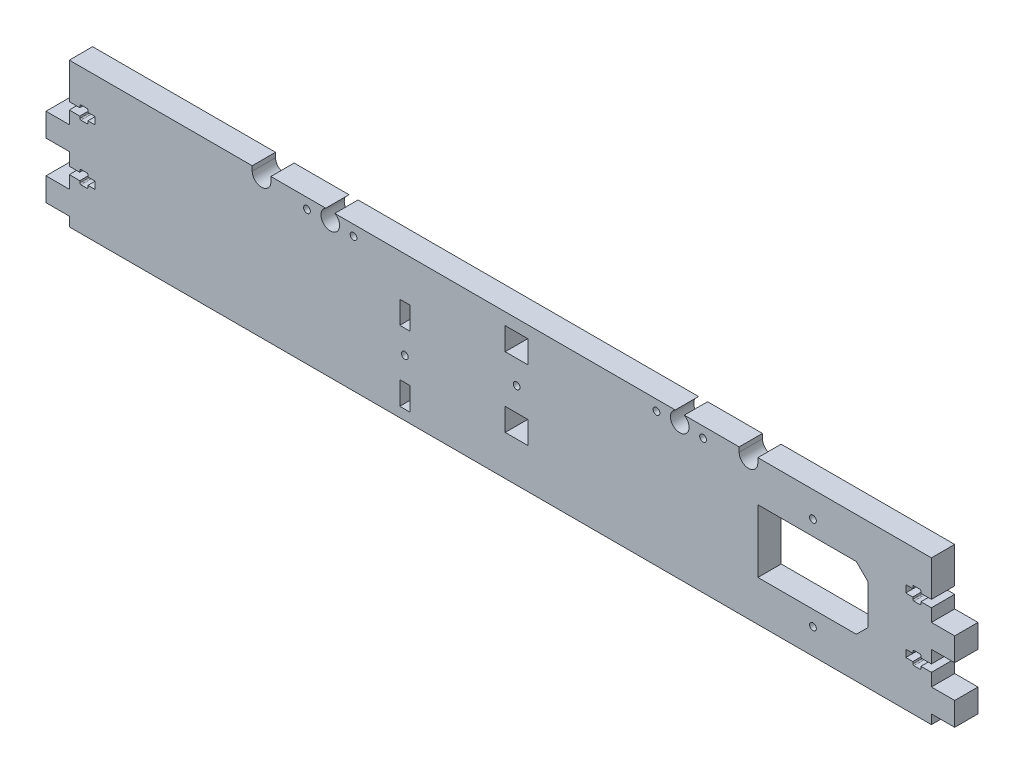
SolidWorks part; units mm, degrees
ref_plane "Front Plane" through (0, 0, 0) normal (0, 0, 1) x (1, 0, 0)
ref_plane "Top Plane" through (0, 0, 0) normal (0, 1, 0) x (1, 0, 0)
ref_plane "Right Plane" through (0, 0, 0) normal (1, 0, 0) x (0, 0, -1)
sketch "Sketch1" plane through (0, 0, 0) normal (0, 0, 1) x (1, 0, 0)
  line L0 (0, 0) -> (-185, 0)
  line L1 (-185, 0) -> (-185, -62) construction
  line L2 (0, -62) -> (-185, -62)
  line L3 (-185, -62) -> (-185, -58)
  line L4 (-185, -58) -> (-195, -58)
  line L5 (-195, -58) -> (-195, -48)
  line L6 (-195, -48) -> (-185, -48)
  line L7 (-185, -48) -> (-185, -34)
  line L8 (-185, -34) -> (-195, -34)
  line L9 (-195, -34) -> (-195, -24)
  line L10 (-195, -24) -> (-185, -24)
  line L11 (0, -62) -> (0, 0)
  line L12 (-185, -24) -> (-185, 0)
  line L13 (-195, -58) -> (-195, -24) construction
  line L14 (-195, -29) -> (-185, -29) construction
  line L15 (-195, -53) -> (-185, -53) construction
  dimension "D1" = 185
  dimension "D2" = 10
  dimension "D3" = 10
  dimension "D4" = 10
  dimension "D5" = 24
  dimension "D6" = 29
  dimension "D7" = 62
extrude "MainBody" add sketch "Sketch1" along normal blind 10
sketch "Sketch3" plane through (0, 0, 10) normal (0, 0, 1) x (1, 0, 0)
  line L0 (-185, -17) -> (-174, -17) construction
  line L1 (-185, 0) -> (-185, -24) construction
  line L2 (-185, -18.55) -> (-180.5, -18.55)
  line L3 (-180.5, -18.55) -> (-180.5, -19.35)
  line L4 (-180, -19.85) -> (-177.5, -19.85)
  line L5 (-177, -19.35) -> (-177, -18.55)
  line L6 (-177, -18.55) -> (-174, -18.55)
  line L7 (-174, -18.55) -> (-174, -15.45)
  line L8 (-180.5, -18.55) -> (-177, -18.55) construction
  line L9 (-195, -24) -> (-195, -34) construction
  line L10 (-180.5, -15.45) -> (-177, -15.45) construction
  line L11 (-177, -15.45) -> (-174, -15.45)
  line L12 (-177, -14.65) -> (-177, -15.45)
  line L13 (-180, -14.15) -> (-177.5, -14.15)
  line L14 (-180.5, -15.45) -> (-180.5, -14.65)
  line L15 (-185, -15.45) -> (-180.5, -15.45)
  line L16 (-185, -18.55) -> (-185, -15.45)
  line L17 (-185, -24) -> (-185, -34) construction
  line L19 (-195, -24) -> (-195, -34) construction
  line L20 (-195, -29) -> (-185, -29) construction
  line L21 (-180.5, -42.55) -> (-177, -42.55) construction
  line L22 (-180.5, -39.45) -> (-177, -39.45) construction
  line L23 (-185, -41) -> (-174, -41) construction
  line L24 (-185, -39.45) -> (-185, -42.55)
  line L25 (-185, -42.55) -> (-180.5, -42.55)
  line L26 (-180.5, -42.55) -> (-180.5, -43.35)
  line L27 (-180, -43.85) -> (-177.5, -43.85)
  line L28 (-177, -43.35) -> (-177, -42.55)
  line L29 (-177, -42.55) -> (-174, -42.55)
  line L30 (-174, -39.45) -> (-174, -42.55)
  line L31 (-177, -39.45) -> (-174, -39.45)
  line L32 (-177, -38.65) -> (-177, -39.45)
  line L33 (-180, -38.15) -> (-177.5, -38.15)
  line L34 (-180.5, -39.45) -> (-180.5, -38.65)
  line L35 (-185, -39.45) -> (-180.5, -39.45)
  line L36 (-180.5, -15.45) -> (-177, -15.45) construction
  arc A0 (-177.5, -19.85) -> (-177, -19.35) centre (-177.5, -19.35) ccw
  arc A1 (-180.5, -19.35) -> (-180, -19.85) centre (-180, -19.35) ccw
  arc A2 (-180.5, -14.65) -> (-180, -14.15) centre (-180, -14.65) cw
  arc A3 (-177.5, -14.15) -> (-177, -14.65) centre (-177.5, -14.65) cw
  arc A4 (-177.5, -43.85) -> (-177, -43.35) centre (-177.5, -43.35) ccw
  arc A5 (-180.5, -43.35) -> (-180, -43.85) centre (-180, -43.35) ccw
  arc A6 (-180.5, -38.65) -> (-180, -38.15) centre (-180, -38.65) cw
  arc A7 (-177.5, -38.15) -> (-177, -38.65) centre (-177.5, -38.65) cw
  point P6 (-195, -29)
  point P15 (-177, -19.85)
  point P18 (-180.5, -19.85)
  point P29 (-180.5, -14.15)
  point P30 (-177, -14.15)
  point P62 (-177, -43.85)
  point P63 (-180.5, -43.85)
  point P64 (-180.5, -38.15)
  point P65 (-177, -38.15)
  dimension "D2" = 8
  dimension "D7" = 0.5
  dimension "D1" = 11
  dimension "D3" = 1.55
  dimension "D4" = 2.85
  dimension "D5" = 12
  dimension "D6" = 3.5
extrude "ScrewCutouts" cut sketch "Sketch3" against normal through all
mirror "Mirror1" about plane through (0, 0, 0) normal (1, 0, 0) of "ScrewCutouts", "MainBody"
sketch "Sketch2" plane through (0, 0, 10) normal (0, 0, 1) x (1, 0, 0)
  line L0 (0, 0) -> (0, -62) construction
  line L1 (-185, -62) -> (185, -62) construction
  line L2 (2, 0) -> (2, -62) construction
  line L3 (185, 0) -> (-185, 0) construction
  line L4 (-63, -4.5) -> (-83, -4.5) construction
  line L5 (-73, -7.5) -> (-73, 0.5) construction
  line L6 (77, -7.5) -> (77, 0.5) construction
  line L7 (67, -4.5) -> (87, -4.5) construction
  circle A0 centre (-73, -3.5) radius 4
  circle A1 centre (-83, -4.5) radius 1.45
  circle A2 centre (-63, -4.5) radius 1.45
  circle A3 centre (67, -4.5) radius 1.45
  circle A4 centre (87, -4.5) radius 1.45
  circle A5 centre (77, -3.5) radius 4
  dimension "D1" = 2.9
  dimension "D2" = 8
  dimension "D4" = 3.5
  dimension "D5" = 75
  dimension "D6" = 2
  dimension "D3" = 10
  dimension "D7" = 1
extrude "RodCutouts" cut sketch "Sketch2" against normal through all
sketch "Sketch4" plane through (0, 0, 10) normal (0, 0, 1) x (1, 0, 0)
  line L0 (77, -3.5) -> (-73, -3.5) construction
  line L1 (2, -3.5) -> (2, -62) construction
  line L2 (-185, -62) -> (185, -62) construction
  line L3 (7, -44.85) -> (7, -5.15) construction
  line L4 (75.0635, 0) -> (-71.0635, 0) construction
  line L5 (7, -10) -> (7, -40) construction
  line L6 (2.075, -5.15) -> (11.925, -5.15)
  line L7 (2.075, -5.15) -> (2.075, -14.85)
  line L8 (2.075, -14.85) -> (11.925, -14.85)
  line L9 (11.925, -5.15) -> (11.925, -14.85)
  line L10 (2.075, -5.15) -> (11.925, -14.85) construction
  line L11 (2.075, -14.85) -> (11.925, -5.15) construction
  line L12 (2.075, -35.15) -> (11.925, -35.15)
  line L13 (2.075, -35.15) -> (2.075, -44.85)
  line L14 (2.075, -44.85) -> (11.925, -44.85)
  line L15 (11.925, -35.15) -> (11.925, -44.85)
  line L16 (2.075, -35.15) -> (11.925, -44.85) construction
  line L17 (2.075, -44.85) -> (11.925, -35.15) construction
  circle A0 centre (7, -25) radius 1.45
  point P12 (7, -10)
  point P17 (7, -40)
  dimension "D8" = 2.9
  dimension "D1" = 9.85
  dimension "D2" = 9.7
  dimension "D3" = 9.85
  dimension "D4" = 9.7
  dimension "D5" = 30
  dimension "D6" = 10
  dimension "D7" = 5
extrude "Cut-Extrude3" cut sketch "Sketch4" against normal through all
sketch "Sketch5" plane through (0, 0, 10) normal (0, 0, 1) x (1, 0, 0)
  line L0 (-41, 0) -> (-41, -62) construction
  line L1 (-74.9365, 0) -> (-185, 0) construction
  line L2 (-185, -62) -> (185, -62) construction
  line L3 (-43.175, -27.65) -> (-43.175, -47.85) construction
  line L4 (-43.175, -17.95) -> (-38.825, -17.95)
  line L5 (-43.175, -17.95) -> (-43.175, -27.65)
  line L6 (-43.175, -27.65) -> (-38.825, -27.65)
  line L7 (-38.825, -17.95) -> (-38.825, -27.65)
  line L8 (-43.175, -17.95) -> (-38.825, -27.65) construction
  line L9 (-43.175, -27.65) -> (-38.825, -17.95) construction
  line L10 (-43.175, -47.85) -> (-38.825, -47.85)
  line L11 (-43.175, -47.85) -> (-43.175, -57.75)
  line L12 (-43.175, -57.75) -> (-38.825, -57.75)
  line L13 (-38.825, -47.85) -> (-38.825, -57.75)
  line L14 (-43.175, -47.85) -> (-38.825, -57.75) construction
  line L15 (-43.175, -57.75) -> (-38.825, -47.85) construction
  line L16 (-38.825, -47.85) -> (-38.825, -27.65) construction
  line L17 (-43.175, -37.75) -> (-38.825, -37.75) construction
  line L18 (-73, -3.5) -> (77, -3.5) construction
  line L19 (2, -3.5) -> (2, -62) construction
  line L20 (2, -32.75) -> (-195, -32.75) construction
  line L21 (-195, -24) -> (-195, -34) construction
  line L22 (-34.625, 8.9944) -> (-34.625, 5) construction
  line L23 (75.0635, 0) -> (-71.0635, 0) construction
  line L24 (-31.425, 8.9944) -> (-31.425, 5)
  line L25 (-37.825, 8.9944) -> (-37.825, 5)
  circle A0 centre (-41, -37.75) radius 1.45
  arc A1 (-31.425, 8.9944) -> (-37.825, 8.9944) centre (-34.625, 8.9944) ccw
  arc A2 (-37.825, 5) -> (-31.425, 5) centre (-34.625, 5) ccw
  point P6 (-41, -22.8)
  point P11 (-41, -52.8)
  point P34 (-34.625, 6.9972)
  dimension "D4" = 9.7
  dimension "D5" = 30
  dimension "D6" = 2.9
  dimension "D9" = 3.2
  dimension "D1" = 4.35
  dimension "D2" = 0
  dimension "D3" = 9.9
  dimension "D7" = 43
  dimension "D8" = 5
  dimension "D10" = 5
  dimension "D11" = 1
extrude "EndstopHolder" cut sketch "Sketch5" against normal through all
sketch "Sketch6" plane through (0, 0, 10) normal (0, 0, 1) x (1, 0, 0)
  line L0 (-43.175, -47.85) -> (-43.175, -27.65) construction
  line L1 (-42.35, -47.85) -> (-30.825, -47.85) construction
  line L3 (-30.825, -53.85) -> (-30.825, -41.85) construction
  line L4 (-32.825, -53.85) -> (-32.825, -41.85)
  line L5 (-28.825, -53.85) -> (-28.825, -41.85)
  line L6 (-38.825, -47.85) -> (-43.175, -47.85) construction
  line L7 (-38.825, -57.75) -> (-38.825, -47.85) construction
  arc A0 (-32.825, -53.85) -> (-28.825, -53.85) centre (-30.825, -53.85) ccw
  arc A1 (-28.825, -41.85) -> (-32.825, -41.85) centre (-30.825, -41.85) ccw
  point P10 (-30.825, -47.85)
  dimension "D1" = 2
  dimension "D2" = 12
  dimension "D3" = 8
  dimension "D4" = 0
extrude "EndstopWires" [suppressed] cut sketch "Sketch6" against normal through all
sketch "Sketch7" plane through (0, 0, 10) normal (0, 0, 1) x (1, 0, 0)
  line L0 (-73, -3.5) -> (77, -3.5) construction
  line L1 (2, -3.5) -> (2, -62) construction
  line L3 (-102.5, 0) -> (-102.5, -2) construction
  line L4 (-74.9365, 0) -> (-185, 0) construction
  line L5 (-98.5, 0) -> (-98.5, -2)
  line L6 (-106.5, 0) -> (-106.5, -2)
  line L7 (106.5, 0) -> (106.5, -2) construction
  line L8 (102.5, 0) -> (102.5, -2)
  line L9 (110.5, 0) -> (110.5, -2)
  line L10 (-185, -62) -> (185, -62) construction
  arc A0 (-98.5, 0) -> (-106.5, 0) centre (-102.5, 0) ccw
  arc A1 (-106.5, -2) -> (-98.5, -2) centre (-102.5, -2) ccw
  arc A2 (102.5, 0) -> (110.5, 0) centre (106.5, 0) cw
  arc A3 (110.5, -2) -> (102.5, -2) centre (106.5, -2) cw
  point P12 (-102.5, -1)
  point P19 (106.5, -1)
  dimension "D3" = 4
  dimension "D1" = 2
  dimension "D2" = 104.5
extrude "Cut-Extrude4" cut sketch "Sketch7" against normal through all
ref_plane "Plane1" through (0, -31, 0) normal (0, 1, 0) x (1, 0, 0)
sketch "Sketch8" plane through (0, 0, 10) normal (0, 0, 1) x (1, 0, 0)
  line L0 (133.7748, 0) -> (133.7748, -62) construction
  line L1 (185, 0) -> (110.5, 0) construction
  line L2 (-185, -62) -> (185, -62) construction
  line L3 (132.2469, -17.485) -> (110.5361, -17.485) construction
  line L4 (151.9576, -17.485) -> (112.5361, -17.485) construction
  line L5 (110.5361, -17.485) -> (110.5361, -44.515)
  line L6 (110.5361, -19.485) -> (110.5361, -42.515) construction
  line L7 (112.5361, -44.515) -> (151.9576, -44.515) construction
  line L8 (110.5361, -44.515) -> (152.7861, -44.515)
  line L9 (152.7861, -44.515) -> (157.7861, -39.515)
  line L10 (157.7861, -39.515) -> (157.7861, -22.485)
  line L11 (157.7861, -22.485) -> (152.7861, -17.485)
  line L12 (152.7861, -17.485) -> (110.5361, -17.485)
  line L13 (157.7861, -38.6866) -> (157.7861, -23.3134) construction
  line L14 (157.2003, -21.8992) -> (153.3719, -18.0708) construction
  line L15 (153.3719, -43.9292) -> (157.2003, -40.1008) construction
extrude "Cut-Extrude5" cut sketch "Sketch8" against normal through all
sketch "Sketch9" plane through (0, 0, 0) normal (0, 0, -1) x (-1, 0, 0)
  line L0 (-105.0611, -31) -> (-163.2611, -31) construction
  line L1 (-105.0611, -43.5977) -> (-105.0611, -18.4023) construction
  line L2 (-163.2611, -18.4023) -> (-163.2611, -43.5977) construction
  circle A0 centre (-134.1611, -11) radius 1.45
  circle A1 centre (-134.1611, -11) radius 1.6 construction
  circle A2 centre (-134.1611, -51) radius 1.45
  dimension "D1" = 2.9
extrude "Cut-Extrude6" cut sketch "Sketch9" against normal through all
equation "\"Y-ROD-SPACING\"=75"
equation "\"D5@Sketch2\"=\"Y-ROD-SPACING\""
equation "\"Y-BED-OFFSET\"=2"
equation "\"D6@Sketch2\"=\"Y-BED-OFFSET\""
equation "\"T-SLOT-NUT-FILLET-RADIUS\"=0.5"
equation "\"D7@Sketch3\"=\"T-SLOT-NUT-FILLET-RADIUS\""
equation "\"T-SLOT-SCREW-SHAFT-RADIUS\"=1.55"
equation "\"D3@Sketch3\"=\"T-SLOT-SCREW-SHAFT-RADIUS\""
equation "\"T-SLOT-SCREW-SHAFT-CUTOUT-LENGTH\"=11"
equation "\"D1@Sketch3\"=\"T-SLOT-SCREW-SHAFT-CUTOUT-LENGTH\""
equation "\"T-SLOT-NUT-DEPTH\"=3.5"
equation "\"D6@Sketch3\"=\"T-SLOT-NUT-DEPTH\""
equation "\"T-SLOT-NUT-WIDTH\"=2.85"
equation "\"D4@Sketch3\"=\"T-SLOT-NUT-WIDTH\""
equation "\"T-SLOT-NUT-END-DISTANCE\"=8"
equation "\"D2@Sketch3\"=\"T-SLOT-NUT-END-DISTANCE\""
equation "\"ACRYLIC-TAB-CUTOUT-SIZE\"=\"ACRYLIC-THICKNESS\"+\"ACRYLIC-TAB-TOLERANCE\"*2"
equation "\"D1@Sketch4\"=\"ACRYLIC-THICKNESS\"-\"KERF\"*2"
equation "\"D2@Sketch4\"=\"ACRYLIC-TAB-WIDTH\"-\"KERF\"*4"
equation "\"D3@Sketch4\"=\"ACRYLIC-THICKNESS\"-\"KERF\"*2"
equation "\"D4@Sketch4\"=\"ACRYLIC-TAB-WIDTH\"-\"KERF\"*4"
equation "\"ACRYLIC-M3-HOLE\"=2.9"
equation "\"D8@Sketch4\"=\"ACRYLIC-M3-HOLE\""
equation "\"Y-BED-ROD-INSET\"=3.5"
equation "\"D1@Sketch2\"=\"ACRYLIC-M3-HOLE\""
equation "\"D4@Sketch2\"=\"Y-BED-ROD-INSET\""
equation "\"SMOOTHROD-CAP-SCREW-DISTANCE\"=20"
equation "\"D3@Sketch2\"=\"SMOOTHROD-CAP-SCREW-DISTANCE\"/2"
equation "\"ACRYLIC-TAB-WIDTH\"=\"ACRYLIC-THICKNESS\""
equation "\"FRAME-WIDTH-INNER\"=370"
equation "\"D2@Sketch1\"=\"ACRYLIC-TAB-WIDTH\""
equation "\"D3@Sketch1\"=\"ACRYLIC-TAB-WIDTH\""
equation "\"D4@Sketch1\"=\"ACRYLIC-TAB-WIDTH\""
equation "\"D1@Sketch1\"=\"FRAME-WIDTH-INNER\"/2"
equation "\"X-ROD-SPACING\"=45"
equation "\"Z-ROD-SPACING\"=17.5"
equation "\"ACRYLIC-THICKNESS\"=10"
equation "\"ACRYLIC-THICKNESS2\"=4.5"
equation "\"NEMA17-HOLE-SPACING\"=31"
equation "\"NEMA17-CENTRAL-CUTOUT\"=22.5"
equation "\"Z-BRACKET-REACH\"=57"
equation "\"TOP-BRACKET-SPACING\"=40"
equation "\"SMOOTHROD-X-LENGTH\"=350"
equation "\"SMOOTHROD-Y-LENGTH\"=350"
equation "\"SMOOTHROD-Z-LENGTH\"=350"
equation "\"SMOOTHROD-TIGHTENING-HEADROOM\"=.25"
equation "\"LEADSCREW-Z-LENGTH\"=300"
equation "\"SCREW-LENGTH-FRAME\"=\"ACRYLIC-THICKNESS\" + 10"
equation "\"SCREW-HEAD-RADIUS\"=6"
equation "\"PRINTED-X-SMOOTHROD-DIAMETER\"=8.8"
equation "\"PRINTED-X-SMOOTHROD-CUTOUT\"=10"
equation "\"PRINTED-X-BASE-HEIGHT\"=10"
equation "\"PRINTED-LM8UU-CUTOUT-SIZE\"=15.5"
equation "\"PRINTED-LM8UU-CUTOUT-LENGTH\"=24.5"
equation "\"PRINTED-X-IDLER-HEIGHT\"=16"
equation "\"PSU-MOUNTING-WIDTH\"=95"
equation "\"PSU-MOUNTING-HEIGHT\"=177"
equation "\"D1@MainBody\"=\"ACRYLIC-THICKNESS\""
equation "\"D1@Sketch5\"=\"ACRYLIC-THICKNESS2\"-\"KERF\"*2"
equation "\"D3@Sketch5\"=\"ACRYLIC-TAB-CUTOUT-SIZE\""
equation "\"D4@Sketch5\"=\"ACRYLIC-TAB-WIDTH\"-\"KERF\"*4"
equation "\"D6@Sketch5\"=\"ACRYLIC-M3-HOLE\""
equation "\"Y-BED-SCREW-SPACING\"=209"
equation "\"Y-BED-SCREW-CUTOUT-SLOT-HEIGHT\"=2"
equation "\"Z-ROD-INSET\"=13.5"
equation "\"Y-BELT-TO-ROD-DISTANCE\"=20"
equation "\"SPOOL-HOLDER-ROD-SPACING\"=150"
equation "\"D1@Sketch7\"=\"Y-BED-SCREW-CUTOUT-SLOT-HEIGHT\""
equation "\"D2@Sketch7\"=\"Y-BED-SCREW-SPACING\"/2"
equation "\"ACRYLIC-TAB-TOLERANCE\"=-.05"
equation "\"SCREW-LENGTH-MOTOR\"=\"ACRYLIC-THICKNESS\" + 5"
equation "\"SCREW-LENGTH-EXTRUDER\"=28"
equation "\"ACRYLIC-X-CARRIAGE-WIDTH\"=55"
equation "\"ACRYLIC-X-CARRIAGE-HEIGHT\"=75"
equation "\"ACRYLIC-X-CARRIAGE-LM8UU-CUTOUT-WIDTH\"=24.25"
equation "\"ACRYLIC-X-CARRIAGE-SCREW-SPACING-X\"=15"
equation "\"ACRYLIC-X-CARRIAGE-SCREW-SPACING-Y\"=33"
equation "\"ACRYLIC-X-CARRIAGE-CENTER-TAB-SPACING\"=14"
equation "\"ACRYLIC-X-CARRIAGE-EXTRUDER-OFFSET\"=26"
equation "\"ACRYLIC-X-CARRIAGE-EXTRUDER-ANGLE\"=90"
equation "\"ACRYLIC-X-CARRIAGE-EXTRUDER-SHELF-DEPTH\"=\"ACRYLIC-X-CARRIAGE-EXTRUDER-OFFSET\" + 28"
equation "\"ACRYLIC-X-CARRIAGE-EXTRUDER-BRACE-SPACING\"=23"
equation "\"ACRYLIC-X-CARRIAGE-EXTRUDER-BRACE-TAB-OFFSET\"=20"
equation "\"ACRYLIC-X-CARRIAGE-EXTRUDER-BRACE-HEIGHT\"=35"
equation "\"ACRYLIC-X-CARRIAGE-EXTRUDER-BRACE-SCREW-SPACING\"=22"
equation "\"PRINTED-M3-HOLE\"=3.5"
equation "\"ACRYLIC-X-CARRIAGE-LM8UU-CUTOUT-HEIGHT\"=11.0"
equation "\"ACRYLIC-X-CARRIAGE-DUAL-WIDTH-MULTIPLIER\"=1.65"
equation "\"ACRYLIC-X-CARRIAGE-DUAL-HOTEND-SPACING\"=42"
equation "\"ACRYLIC-X-CARRIAGE-DUAL-WIDTH\"=75"
equation "\"ACRYLIC-X-CARRIAGE-DUAL-HOTEND-SEPARATION\"=36"
equation "\"ACRYLIC-X-CARRIAGE-DUAL-MOUNT-PLATE-DEPTH\"=75"
equation "\"ACRYLIC-X-CARRIAGE-DUAL-MOUNT-BRACE-WIDTH\"=33"
equation "\"ACRYLIC-X-CARRIAGE-DUAL-MOUNT-SCREW-WIDTH\"=40"
equation "\"BLOWER-FAN-WIDTH\"=15"
equation "\"KERF\"=0.075"
equation "\"PRINTED-M3-NUT-AF\"=6.25"
equation "\"ACRYLIC-X-CARRIAGE-DUAL-FAN-OFFSET\"=52"
equation "\"ACRYLIC-X-CARRIAGE-DUAL-FAN-HEIGHT\"=20"
equation "\"D1@Sketch9\"=\"ACRYLIC-M3-HOLE\""
